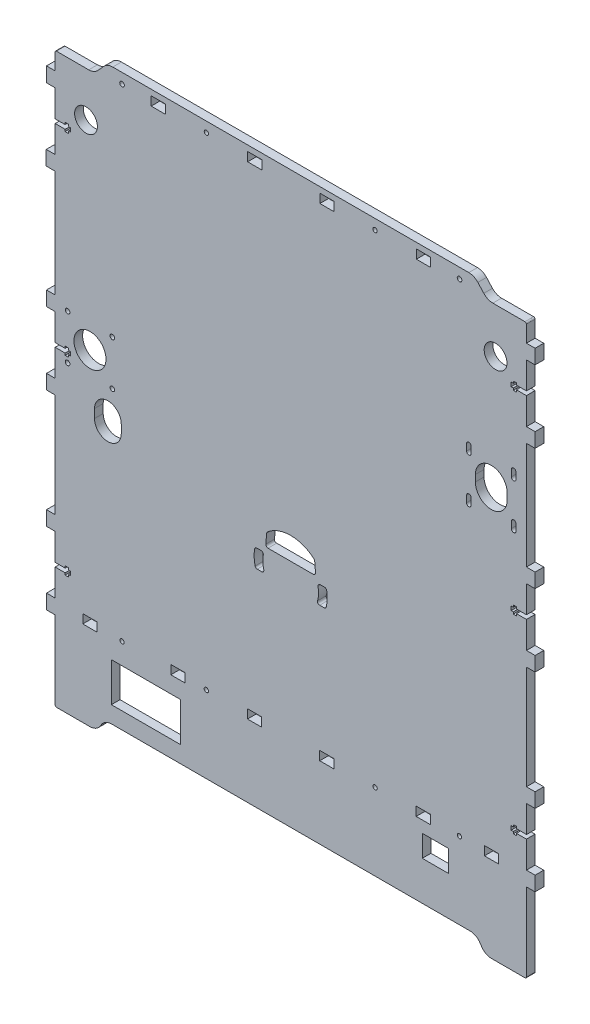
SolidWorks part; units mm, degrees
ref_plane "Спереди" through (0, 0, 0) normal (0, 0, 1) x (1, 0, 0)
ref_plane "Сверху" through (0, 0, 0) normal (0, 1, 0) x (1, 0, 0)
ref_plane "Справа" through (0, 0, 0) normal (1, 0, 0) x (0, 0, -1)
sketch "Эскиз1" plane through (0, 0, 0) normal (0, 0, 1) x (1, 0, 0)
  line L0 (-11.6369, -134.9128) -> (-21.486, -134.9128)
  line L1 (-21.486, -134.9128) -> (-21.486, -128.713)
  line L2 (-11.6369, -128.713) -> (-11.6369, -134.9128)
  line L3 (-21.486, -128.713) -> (-11.6369, -128.713)
  line L4 (-61.6369, -128.7116) -> (-61.6369, -134.9114)
  line L5 (-71.4861, -128.7116) -> (-61.6369, -128.7116)
  line L6 (-71.4861, -134.9114) -> (-71.4861, -128.7116)
  line L7 (-61.6369, -134.9114) -> (-71.4861, -134.9114)
  line L8 (49.4936, -157.9128) -> (49.4936, -142.9128)
  line L9 (49.4936, -142.9128) -> (67.4936, -142.9128)
  line L10 (67.4936, -142.9128) -> (67.4936, -157.9128)
  line L11 (67.4936, -157.9128) -> (49.4936, -157.9128)
  line L12 (-197.6944, 21.333) -> (-197.6944, 19.9601)
  line L13 (-204.6064, 24.1612) -> (-204.6064, 42.7589)
  line L14 (-195.4969, 25.5327) -> (-195.4969, 25.5599)
  line L15 (127.5936, 42.7589) -> (127.5936, 52.7317)
  line L16 (-193.9961, 24.1327) -> (-193.9961, 24.1599)
  line L17 (-195.4961, 24.159) -> (-195.4969, 25.5327)
  line L18 (-195.4944, 21.3327) -> (-195.4944, 21.3599)
  line L19 (-193.9944, 21.3608) -> (-193.9961, 24.1327)
  line L20 (112.4816, 24.1608) -> (112.4816, 24.1338)
  line L21 (114.6816, 24.1606) -> (114.6816, 25.5336)
  line L22 (-195.4936, 19.9601) -> (-195.4944, 21.3327)
  line L23 (110.9833, 21.3609) -> (110.9833, 21.3338)
  line L24 (110.9816, 24.1329) -> (110.9833, 21.3609)
  line L25 (121.5936, 24.1606) -> (121.5936, 42.7589)
  line L26 (-197.6969, 25.5328) -> (-197.6969, 24.16)
  line L27 (127.5936, -7.243) -> (127.5936, 2.7298)
  line L28 (112.4841, 19.9608) -> (112.4841, 19.9338)
  line L29 (-204.6064, 21.333) -> (-204.6064, 21.3602)
  line L30 (121.5936, 52.7317) -> (121.5936, 126.8956)
  line L31 (-210.6064, 42.7589) -> (-210.6064, 52.7317)
  line L32 (-204.6064, 2.7298) -> (-204.6064, 21.333)
  line L33 (-204.6064, 52.7317) -> (-204.6064, 126.8956)
  line L34 (-114.6824, -134.9128) -> (-124.5316, -134.9128)
  line L35 (-124.5316, -134.9128) -> (-124.5316, -128.713)
  line L36 (-124.5316, -128.713) -> (-114.6824, -128.713)
  line L37 (-114.6824, -128.713) -> (-114.6824, -134.9128)
  line L38 (-175.6509, -134.9128) -> (-185.5001, -134.9128)
  line L39 (-185.5001, -134.9128) -> (-185.5001, -128.713)
  line L40 (-185.5001, -128.713) -> (-175.6509, -128.713)
  line L41 (-175.6509, -128.713) -> (-175.6509, -134.9128)
  line L42 (92.5339, -134.9128) -> (102.3831, -134.9128)
  line L43 (102.3831, -134.9128) -> (102.3831, -128.713)
  line L44 (102.3831, -128.713) -> (92.5339, -128.713)
  line L45 (92.5339, -128.713) -> (92.5339, -134.9128)
  line L46 (55.1377, -134.9128) -> (45.2885, -134.9128)
  line L47 (45.2885, -134.9128) -> (45.2885, -128.713)
  line L48 (45.2885, -128.713) -> (55.1377, -128.713)
  line L49 (55.1377, -128.713) -> (55.1377, -134.9128)
  line L50 (-18.1346, -29.194) -> (-21.1843, -29.194)
  line L51 (-21.5365, -41.694) -> (-18.4403, -41.694)
  line L52 (-64.7445, -41.694) -> (-61.6484, -41.694)
  line L53 (-62.0005, -29.194) -> (-65.0502, -29.194)
  line L54 (-58.1883, -16.8245) -> (-58.7957, -23.7669)
  line L55 (-24.3892, -23.7669) -> (-24.9965, -16.8245)
  line L56 (-57.3014, -25.3976) -> (-25.8835, -25.3976)
  line L57 (-165.6924, -146.4128) -> (-165.6924, -173.4128)
  line L58 (-165.6924, -173.4128) -> (-117.6924, -173.4128)
  line L59 (-117.6924, -173.4128) -> (-117.6924, -146.4128)
  line L60 (-117.6924, -146.4128) -> (-165.6924, -146.4128)
  line L61 (-181.3495, 199.306) -> (-203.7824, 199.306)
  line L62 (-170.9813, 206.5447) -> (-175.0792, 202.0673)
  line L63 (127.5936, -128.9629) -> (121.5936, -128.9629)
  line L64 (81.6982, 209.306) -> (-164.711, 209.306)
  line L65 (121.5936, -7.243) -> (127.5936, -7.243)
  line L66 (87.9686, 206.5447) -> (92.0664, 202.0673)
  line L67 (98.3368, 199.306) -> (120.5936, 199.306)
  line L68 (121.5936, 186.9053) -> (121.5936, 198.306)
  line L69 (121.5936, 176.9053) -> (127.5936, 176.9053)
  line L70 (127.5936, 176.9053) -> (127.5936, 186.9053)
  line L71 (-204.6064, 42.7589) -> (-210.6064, 42.7589)
  line L72 (120.5056, -194.0051) -> (97.4692, -194.0051)
  line L73 (91.0458, -190.9688) -> (88.9891, -187.9491)
  line L74 (-203.6944, -194.0051) -> (-180.57, -194.0051)
  line L75 (-210.6064, 176.9053) -> (-210.6064, 187.0477)
  line L76 (114.6816, 158.3008) -> (114.6816, 159.7009)
  line L77 (121.6816, -107.5551) -> (114.6816, -107.5551)
  line L78 (-204.6064, 158.3008) -> (-204.6064, 176.9053)
  line L79 (114.6816, -106.1549) -> (112.4808, -106.1549)
  line L80 (-204.6064, -107.5541) -> (-204.6064, -88.9732)
  line L81 (114.6841, -110.3549) -> (121.5936, -110.3561)
  line L82 (121.6816, -107.5551) -> (121.6816, -88.9732)
  line L83 (110.9833, -110.3548) -> (112.4833, -110.3539)
  line L84 (112.4808, -106.1549) -> (112.4816, -107.5548)
  line L85 (110.9816, -107.5557) -> (110.9833, -110.3548)
  line L86 (-197.6944, -111.7552) -> (-195.4936, -111.7552)
  line L87 (121.5936, 158.3008) -> (114.6816, 158.3008)
  line L88 (114.6841, -111.7549) -> (114.6841, -110.3549)
  line L89 (114.6816, -107.5551) -> (114.6816, -106.1549)
  line L90 (112.4816, -107.5548) -> (110.9816, -107.5557)
  line L91 (112.4833, 155.5019) -> (112.4841, 154.101)
  line L92 (-197.6969, -106.1553) -> (-197.6969, -107.5553)
  line L93 (-204.6064, 21.3602) -> (-197.6944, 21.3602)
  line L94 (-197.6944, 21.3602) -> (-197.6944, 21.333)
  line L95 (-204.6064, 155.4998) -> (-197.6944, 155.4998)
  line L96 (121.5936, -128.9629) -> (121.5936, -110.3561)
  line L97 (121.5936, 2.7298) -> (121.5936, 21.3325)
  line L98 (127.5936, -138.9629) -> (127.5936, -128.9629)
  line L99 (114.6841, 21.3337) -> (121.5936, 21.3325)
  line L100 (-197.6944, 155.4998) -> (-197.6944, 154.0997)
  line L101 (-197.6969, 158.2996) -> (-204.6064, 158.3008)
  line L102 (-195.4961, 158.2986) -> (-195.4969, 159.6996)
  line L103 (112.4833, -110.3539) -> (112.4841, -111.7548)
  line L104 (-197.6969, -107.5553) -> (-204.6064, -107.5541)
  line L105 (112.4808, 159.7009) -> (112.4816, 158.301)
  line L106 (114.6841, 154.101) -> (114.6841, 155.501)
  line L107 (-197.6944, -110.3551) -> (-197.6944, -111.7552)
  line L108 (110.9816, 158.3001) -> (110.9833, 155.5011)
  line L109 (-195.4969, 25.5599) -> (-197.6969, 25.56)
  line L110 (112.4841, 19.9338) -> (114.6841, 19.9337)
  line L111 (112.4841, 154.101) -> (114.6841, 154.101)
  line L112 (110.9833, 155.5011) -> (112.4833, 155.5019)
  line L113 (121.5936, -78.9732) -> (121.5936, -7.243)
  line L114 (-195.4944, 155.4996) -> (-193.9944, 155.5004)
  line L115 (112.4808, 25.5336) -> (112.4816, 24.1608)
  line L116 (114.6816, 24.1335) -> (114.6816, 24.1606)
  line L117 (112.4816, 158.301) -> (110.9816, 158.3001)
  line L118 (-195.4969, -106.1553) -> (-197.6969, -106.1553)
  line L119 (-193.9944, -110.3545) -> (-193.9961, -107.5554)
  line L120 (-195.4944, -110.3553) -> (-193.9944, -110.3545)
  line L121 (-197.6944, 19.9601) -> (-195.4936, 19.9601)
  line L122 (-195.4944, 21.3599) -> (-193.9944, 21.3608)
  line L123 (114.6841, 19.9337) -> (114.6841, 19.9608)
  line L124 (-204.6064, -110.3551) -> (-197.6944, -110.3551)
  line L125 (-195.4961, -107.5563) -> (-195.4969, -106.1553)
  line L126 (-193.9961, 24.1599) -> (-195.4961, 24.159)
  line L127 (-197.6944, 154.0997) -> (-195.4936, 154.0997)
  line L128 (-195.4936, -111.7552) -> (-195.4944, -110.3553)
  line L129 (-197.6969, 159.6996) -> (-197.6969, 158.2996)
  line L130 (-193.9961, -107.5554) -> (-195.4961, -107.5563)
  line L131 (-195.4936, 154.0997) -> (-195.4944, 155.4996)
  line L132 (121.5936, 24.1335) -> (121.5936, 24.1606)
  line L133 (114.6816, 159.7009) -> (112.4808, 159.7009)
  line L134 (-193.9944, 155.5004) -> (-193.9961, 158.2995)
  line L135 (114.6841, 155.501) -> (121.5936, 155.4998)
  line L136 (-197.6969, 24.16) -> (-204.6064, 24.1612)
  line L137 (114.6841, 19.9608) -> (114.6841, 21.3337)
  line L138 (-197.6969, 25.56) -> (-197.6969, 25.5328)
  line L139 (112.4841, -111.7548) -> (114.6841, -111.7549)
  line L140 (112.4816, 24.1338) -> (110.9816, 24.1329)
  line L141 (-195.4969, 159.6996) -> (-197.6969, 159.6996)
  line L142 (121.5936, 158.3008) -> (121.5936, 176.9053)
  line L143 (114.6816, 25.5336) -> (112.4808, 25.5336)
  line L144 (-193.9961, 158.2995) -> (-195.4961, 158.2986)
  line L145 (-204.6064, -7.243) -> (-210.6064, -7.243)
  line L146 (-204.6064, 176.9053) -> (-210.6064, 176.9053)
  line L147 (127.5936, -88.9732) -> (127.5936, -78.9732)
  line L148 (110.9833, 21.3338) -> (112.4833, 21.3347)
  line L149 (121.5936, 24.1335) -> (114.6816, 24.1335)
  line L150 (112.4833, 21.3347) -> (112.4841, 19.9608)
  line L151 (-204.6064, -193.0051) -> (-204.6064, -139.0561)
  line L152 (-204.6064, 136.8956) -> (-204.6064, 155.4998)
  line L153 (-210.7824, 126.8956) -> (-210.7824, 136.8956)
  line L154 (-204.6064, 126.8956) -> (-210.7824, 126.8956)
  line L155 (127.5936, 126.8956) -> (127.5936, 136.8956)
  line L156 (127.5936, 136.8956) -> (121.5936, 136.8956)
  line L157 (-138.1414, 205.3634) -> (-128.2923, 205.3634)
  line L158 (-128.2923, 205.3634) -> (-128.2923, 199.1636)
  line L159 (-128.2923, 199.1636) -> (-138.1414, 199.1636)
  line L160 (-138.1414, 199.1636) -> (-138.1414, 205.3634)
  line L161 (55.2545, 199.1636) -> (45.4053, 199.1636)
  line L162 (45.4053, 199.1636) -> (45.4053, 205.3634)
  line L163 (45.4053, 205.3634) -> (55.2545, 205.3634)
  line L164 (55.2545, 205.3634) -> (55.2545, 199.1636)
  line L165 (-61.5189, 199.1636) -> (-71.3681, 199.1636)
  line L166 (-71.3681, 199.1636) -> (-71.3681, 205.3634)
  line L167 (-71.3681, 205.3634) -> (-61.5189, 205.3634)
  line L168 (-61.5189, 205.3634) -> (-61.5189, 199.1636)
  line L169 (-11.5189, 199.1636) -> (-21.3681, 199.1636)
  line L170 (-21.3681, 199.1636) -> (-21.3681, 205.3634)
  line L171 (-21.3681, 205.3634) -> (-11.5189, 205.3634)
  line L172 (-11.5189, 205.3634) -> (-11.5189, 199.1636)
  line L173 (127.5936, 186.9053) -> (121.5936, 186.9053)
  line L174 (121.5936, 136.8956) -> (121.5936, 155.4998)
  line L175 (121.5936, 126.8956) -> (127.5936, 126.8956)
  line L176 (-210.6064, 2.7298) -> (-204.6064, 2.7298)
  line L177 (-204.6064, -128.9629) -> (-204.6064, -110.3551)
  line L178 (-204.6064, -78.9732) -> (-204.6064, -7.243)
  line L179 (-210.6064, -128.9629) -> (-204.6064, -128.9629)
  line L180 (-210.6064, -88.9732) -> (-210.6064, -78.9732)
  line L181 (-210.6064, -7.243) -> (-210.6064, 2.7298)
  line L182 (-210.6064, -78.9732) -> (-204.6064, -78.9732)
  line L183 (-174.0586, -190.9688) -> (-172.0019, -187.9491)
  line L184 (127.5936, 52.7317) -> (121.5936, 52.7317)
  line L185 (121.5936, -193.0051) -> (121.5936, -138.9629)
  line L186 (-165.4905, -184.9128) -> (82.4778, -184.9128)
  line L187 (-210.6064, -139.0561) -> (-210.6064, -128.9629)
  line L188 (-204.6064, -139.0561) -> (-210.6064, -139.0561)
  line L189 (-210.7824, 136.8956) -> (-204.6064, 136.8956)
  line L190 (-210.6064, 187.0477) -> (-204.6064, 187.0477)
  line L191 (-210.6064, 52.7317) -> (-204.6064, 52.7317)
  line L192 (-204.6064, -88.9732) -> (-210.6064, -88.9732)
  line L193 (121.5936, -138.9629) -> (127.5936, -138.9629)
  line L194 (127.5936, -78.9732) -> (121.5936, -78.9732)
  line L195 (127.5936, 2.7298) -> (121.5936, 2.7298)
  line L196 (-204.6064, 187.0477) -> (-204.6064, 198.306)
  line L197 (121.5936, 42.7589) -> (127.5936, 42.7589)
  line L198 (121.6816, -88.9732) -> (127.5936, -88.9732)
  line L199 (-158.8564, -7.694) -> (-158.8564, -1.694)
  line L200 (86.2572, 90.556) -> (86.2572, 86.056)
  line L201 (111.1572, 75.056) -> (111.1572, 70.556)
  line L202 (108.2572, 86.056) -> (108.2572, 90.556)
  line L203 (114.3572, 101.556) -> (114.3572, 106.056)
  line L204 (111.1572, 106.056) -> (111.1572, 101.556)
  line L205 (114.3572, 70.556) -> (114.3572, 75.056)
  line L206 (80.1572, 75.056) -> (80.1572, 70.556)
  line L207 (83.3572, 70.556) -> (83.3572, 75.056)
  line L208 (83.3572, 101.556) -> (83.3572, 106.056)
  line L209 (-177.3564, -1.694) -> (-177.3564, -7.694)
  line L210 (80.1572, 106.056) -> (80.1572, 101.556)
  arc A0 (80.1572, 70.556) -> (83.3572, 70.556) centre (81.7572, 70.556) ccw
  arc A1 (80.1572, 101.556) -> (83.3572, 101.556) centre (81.7572, 101.556) ccw
  circle A2 centre (-183.2564, 168.306) radius 7.9
  circle A3 centre (100.2436, 168.306) radius 7.9
  arc A4 (-16.6559, -30.4419) -> (-18.1346, -29.194) centre (-18.1346, -30.694) ccw
  arc A5 (-21.1843, -29.194) -> (-22.6563, -30.9825) centre (-21.1843, -30.694) ccw
  arc A6 (-22.9831, -39.7973) -> (-22.6563, -30.9825) centre (-41.5924, -34.694) ccw
  arc A7 (-22.9831, -39.7973) -> (-21.5365, -41.694) centre (-21.5365, -40.194) ccw
  arc A8 (-65.0502, -29.194) -> (-66.5289, -30.4419) centre (-65.0502, -30.694) ccw
  arc A9 (-66.5289, -30.4419) -> (-66.2039, -40.5407) centre (-41.5924, -34.694) ccw
  arc A10 (-66.2039, -40.5407) -> (-64.7445, -41.694) centre (-64.7445, -40.194) ccw
  arc A11 (-61.6484, -41.694) -> (-60.2018, -39.7973) centre (-61.6484, -40.194) ccw
  arc A12 (-60.5285, -30.9825) -> (-60.2018, -39.7973) centre (-41.5924, -34.694) ccw
  arc A13 (-60.5285, -30.9825) -> (-62.0005, -29.194) centre (-62.0005, -30.694) ccw
  arc A14 (-16.9809, -40.5407) -> (-16.6559, -30.4419) centre (-41.5924, -34.694) ccw
  arc A15 (-18.4403, -41.694) -> (-16.9809, -40.5407) centre (-18.4403, -40.194) ccw
  arc A16 (-57.6664, -15.8131) -> (-58.1883, -16.8245) centre (-56.694, -16.9552) ccw
  arc A17 (-25.5185, -15.8131) -> (-57.6664, -15.8131) centre (-41.5924, -34.694) ccw
  arc A18 (-24.9965, -16.8245) -> (-25.5185, -15.8131) centre (-26.4908, -16.9552) ccw
  arc A19 (-25.8835, -25.3976) -> (-24.3892, -23.7669) centre (-25.8835, -23.8976) ccw
  arc A20 (-58.7957, -23.7669) -> (-57.3014, -25.3976) centre (-57.3014, -23.8976) ccw
  circle A21 centre (-158.3064, 202.256) radius 1.6
  arc A22 (-203.7824, 199.306) -> (-204.6064, 198.306) centre (-203.6944, 198.394) ccw
  arc A23 (-181.3495, 199.306) -> (-175.0792, 202.0673) centre (-181.3495, 207.806) ccw
  arc A24 (-164.711, 209.306) -> (-170.9813, 206.5447) centre (-164.711, 200.806) ccw
  circle A25 centre (75.2936, 202.256) radius 1.6
  arc A26 (87.9686, 206.5447) -> (81.6982, 209.306) centre (81.6982, 200.806) ccw
  arc A27 (-180.57, -194.0051) -> (-174.0586, -190.9688) centre (-180.57, -185.5051) ccw
  arc A28 (120.5056, -194.0051) -> (121.5936, -193.0051) centre (120.5496, -192.9611) ccw
  arc A29 (-165.4905, -184.9128) -> (-172.0019, -187.9491) centre (-165.4905, -193.4128) ccw
  arc A30 (-204.6064, -193.0051) -> (-203.6944, -194.0051) centre (-203.6504, -193.0491) ccw
  arc A31 (88.9891, -187.9491) -> (82.4778, -184.9128) centre (82.4778, -193.4128) ccw
  arc A32 (91.0458, -190.9688) -> (97.4692, -194.0051) centre (97.5132, -185.5994) ccw
  arc A33 (121.5936, 198.306) -> (120.5936, 199.306) centre (120.5936, 198.306) ccw
  arc A34 (92.0664, 202.0673) -> (98.3368, 199.306) centre (98.3368, 207.806) ccw
  circle A35 centre (16.8336, 202.3598) radius 1.5
  circle A36 centre (-99.9157, 202.3598) radius 1.5
  circle A37 centre (-196.0064, 47.306) radius 1.6
  arc A38 (-177.3564, -7.694) -> (-158.8564, -7.694) centre (-168.1064, -7.694) ccw
  circle A39 centre (-165.0064, 16.306) radius 1.6
  circle A40 centre (-196.0064, 16.306) radius 1.6
  arc A41 (86.2572, 86.056) -> (108.2572, 86.056) centre (97.2572, 86.056) ccw
  arc A42 (108.2572, 90.556) -> (86.2572, 90.556) centre (97.2572, 90.556) ccw
  arc A43 (114.3572, 75.056) -> (111.1572, 75.056) centre (112.7572, 75.056) ccw
  circle A44 centre (-180.5064, 31.806) radius 11.1
  circle A45 centre (-165.0064, 47.306) radius 1.6
  arc A46 (114.3572, 106.056) -> (111.1572, 106.056) centre (112.7572, 106.056) ccw
  arc A47 (111.1572, 101.556) -> (114.3572, 101.556) centre (112.7572, 101.556) ccw
  arc A48 (111.1572, 70.556) -> (114.3572, 70.556) centre (112.7572, 70.556) ccw
  arc A49 (83.3572, 75.056) -> (80.1572, 75.056) centre (81.7572, 75.056) ccw
  arc A50 (-158.8564, -1.694) -> (-177.3564, -1.694) centre (-168.1064, -1.694) ccw
  arc A51 (83.3572, 106.056) -> (80.1572, 106.056) centre (81.7572, 106.056) ccw
  circle A52 centre (75.2316, -131.7306) radius 1.5
  circle A53 centre (16.8441, -131.6894) radius 1.5
  circle A54 centre (-99.9433, -131.7314) radius 1.5
  circle A55 centre (-158.2786, -131.7671) radius 1.5
extrude "Бобышка-Вытянуть1" add sketch "Эскиз1" along normal blind 6
